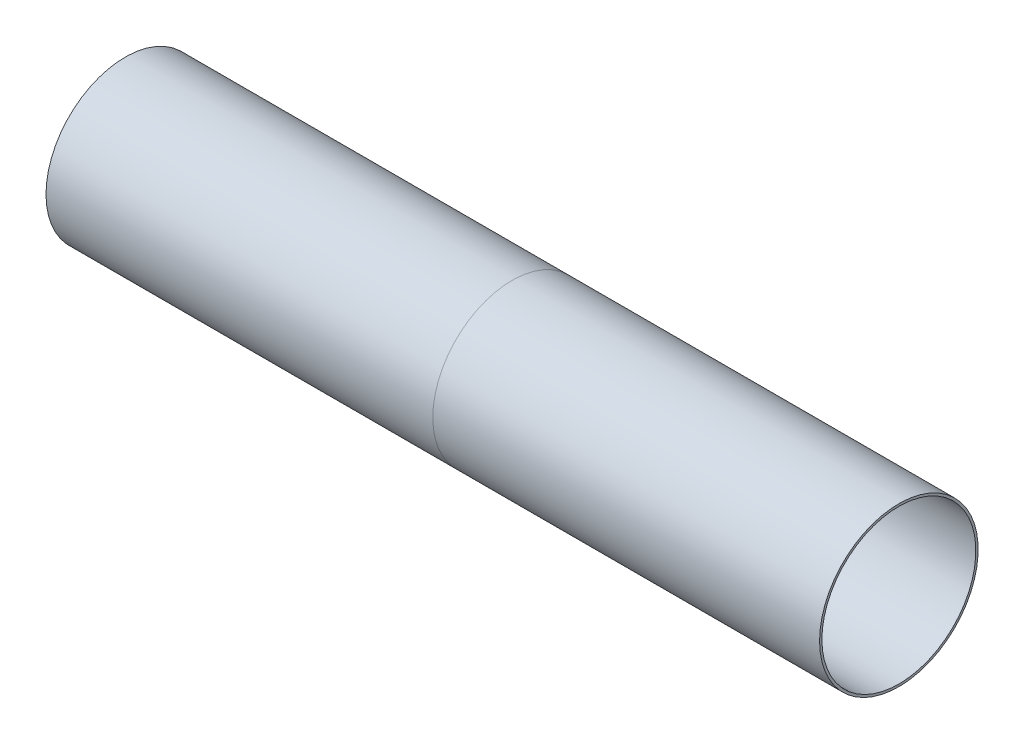
SolidWorks part; units mm, degrees
other "End Part"
other "Middle Bit"
other "Coupler"
ref_plane "Front Plane" through (0, 0, 0) normal (0, 0, 1) x (1, 0, 0)
ref_plane "Top Plane" through (0, 0, 0) normal (0, 1, 0) x (1, 0, 0)
ref_plane "Right Plane" through (0, 0, 0) normal (1, 0, 0) x (0, 0, -1)
sketch "Sketch2" plane through (0, 0, 0) normal (0, 1, 0) x (1, 0, 0)
  line L0 (0, 0) -> (200, 0)
  line L1 (200, 39.8) -> (200, 0) construction
  line L2 (0, 39.8) -> (0, 0) construction
  line L3 (200, 41) -> (0, 41)
  line L4 (200, 41) -> (200, 39.8)
  line L5 (200, 39.8) -> (0, 39.8)
  line L6 (0, 41) -> (0, 39.8)
  line L7 (100, 39.8) -> (100, 41) construction
  line L8 (200, 40.4) -> (0, 40.4) construction
  line L9 (0, 39.8) -> (11.4301, 38.8)
  line L10 (11.4301, 38.8) -> (12.4301, 39.8)
  line L11 (11.4301, 38.8) -> (11.4301, 39.8) construction
  line L12 (-12.4301, 39.8) -> (12.4301, 39.8)
  line L13 (0, 39.8) -> (-11.4301, 38.8)
  line L14 (-11.4301, 38.8) -> (-12.4301, 39.8)
  line L15 (-200, 39.8) -> (0, 39.8)
  line L16 (-200, 41) -> (0, 41)
  line L17 (-200, 41) -> (-200, 39.8)
  line L18 (-100, 41) -> (-100, 0) construction
  line L19 (-187.5699, 39.8) -> (-200, 39.8)
  line L20 (-188.5699, 38.8) -> (-187.5699, 39.8)
  line L21 (-200, 39.8) -> (-188.5699, 38.8)
  point P328 (100, 40.4)
  dimension "D1" = 200
  dimension "D2" = 39.8
  dimension "D3" = 1.2
  dimension "D4" = 45
  dimension "D5" = 5
  dimension "D6" = 1
revolve "Revolve1" add sketch "Sketch2" angle 360 about L0 region at (100, 0, -40.4) region at (7.9534, 0, -39.4667)
revolve "Revolve2" add sketch "Sketch2<3>" angle 360 about L0 region at (-100, 0, -40.4) region at (-7.9534, 0, -39.4667)
sketch "Sketch2<3>" plane through (0, 0, 0) normal (0, 1, 0) x (1, 0, 0) same geometry as "Sketch2"
sketch "Sketch3" plane through (0, 0, 0) normal (0, 1, 0) x (1, 0, 0)
  line L0 (-11.4301, 38.8) -> (0, 39.8)
  line L1 (0, 39.8) -> (11.4301, 38.8)
  line L2 (11.4301, 38.8) -> (11.4301, 37.6)
  line L3 (11.4301, 37.6) -> (-11.4301, 37.6)
  line L4 (-11.4301, 37.6) -> (-11.4301, 38.8)
  dimension "D1" = 1.2
revolve "Revolve3" add sketch "Sketch3" angle 360 about L0
